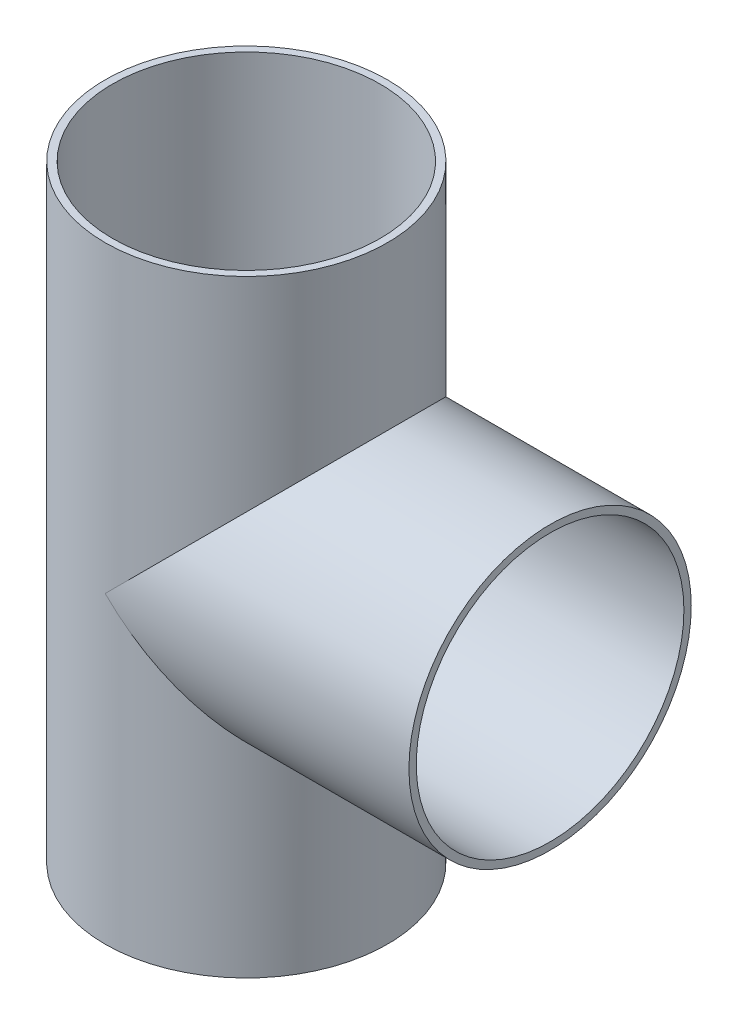
SolidWorks part; units mm, degrees
ref_plane "Front Plane" through (0, 0, 0) normal (0, 0, 1) x (1, 0, 0)
ref_plane "Top Plane" through (0, 0, 0) normal (0, 1, 0) x (1, 0, 0)
ref_plane "Right Plane" through (0, 0, 0) normal (1, 0, 0) x (0, 0, -1)
sketch "Sketch1" plane through (0, 0, 0) normal (0, 1, 0) x (1, 0, 0)
  circle A0 centre (0, 0) radius 31.75
  dimension "D1" = 63.5
extrude "Extrude1" add sketch "Sketch1" along normal blind 68.326 and the other way blind 68.326
sketch "Sketch2" plane through (0, 0, 0) normal (0, 1, 0) x (1, 0, 0)
  line L0 (0, 0) -> (68.326, 0)
  dimension "D1" = 68.326
ref_plane "Plane1" through (68.326, 0, 0) normal (1, 0, 0) x (0, 0, -1)
sketch "Sketch3" plane through (68.326, 0, 0) normal (1, 0, 0) x (0, 0, -1)
  circle A0 centre (0, 0) radius 31.75
  dimension "D1" = 63.5
extrude "Extrude2" add sketch "Sketch3" against normal up to body separate body
sketch "Sketch4" plane through (68.326, 0, 0) normal (1, 0, 0) x (0, 0, -1)
  circle A0 centre (0, 0) radius 30.099
  dimension "D1" = 60.198
extrude "Cut-Extrude1" cut sketch "Sketch4" against normal up to vertex (68.326 mm away) up to point (0, 0, 0)
sketch "Sketch5" plane through (0, 0, 0) normal (0, 1, 0) x (1, 0, 0)
  circle A0 centre (0, 0) radius 30.099
  dimension "D1" = 60.198
extrude "Cut-Extrude2" cut sketch "Sketch5" against normal through all and the other way through all
ref_plane "Plane2" through (0, 0, 0) normal (1, 0, 0) x (0, 0, -1)
